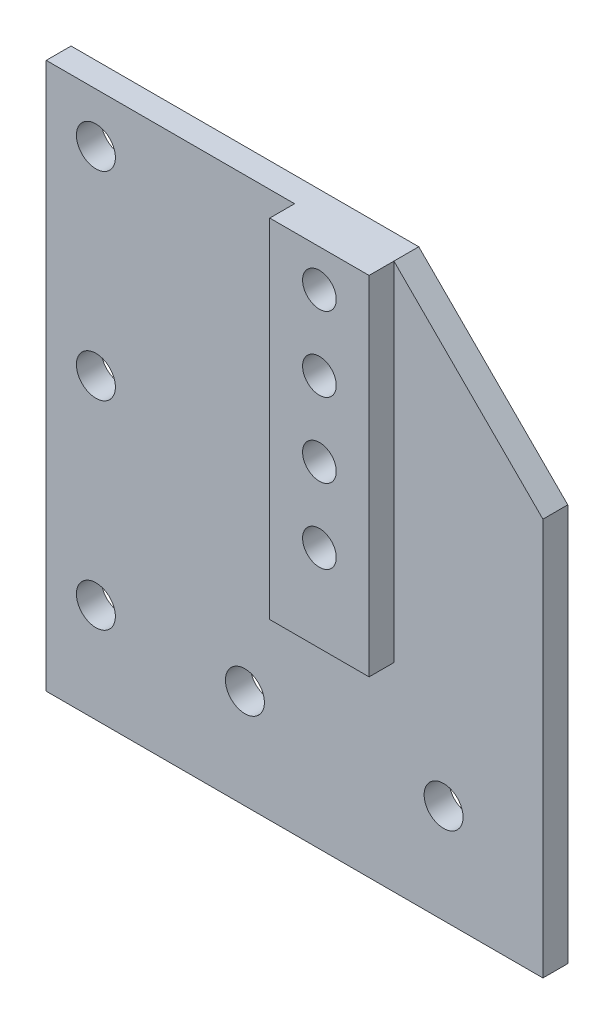
SolidWorks part; units mm, degrees
ref_plane "Front Plane" through (0, 0, 0) normal (0, 0, 1) x (1, 0, 0)
ref_plane "Top Plane" through (0, 0, 0) normal (0, 1, 0) x (1, 0, 0)
ref_plane "Right Plane" through (0, 0, 0) normal (1, 0, 0) x (0, 0, -1)
sketch "Sketch1" plane through (0, 0, 0) normal (0, 0, 1) x (1, 0, 0)
  line L0 (-254, -12.7) -> (-266.7, -12.7)
  line L2 (-266.7, 57.15) -> (-254, 57.15)
  line L3 (-254, -16.7024) -> (-254, 609.6) construction
  line L4 (-254, -12.7) -> (-203.2, -12.7)
  line L5 (-254, 57.15) -> (-222.25, 57.15)
  line L6 (-203.2, -12.7) -> (-203.2, 12.7)
  line L7 (-254, 12.7) -> (254, 12.7) construction
  line L13 (-222.25, 57.15) -> (-203.2, 38.1)
  line L15 (-266.7, -12.7) -> (-266.7, 57.15)
  line L16 (-266.7, 609.6) -> (-266.7, -16.7024) construction
  line L17 (-203.2, 12.7) -> (-203.2, 38.1)
  dimension "D1" = 69.85
  dimension "D2" = 25.4
  dimension "D3" = 31.75
extrude "Boss-Extrude1" add sketch "Sketch1" along normal blind 3.175
sketch "Sketch2" plane through (0, 0, 3.175) normal (0, 0, 1) x (1, 0, 0)
  line L0 (-203.2, -12.7) -> (-203.2, 12.7) construction
  line L1 (-215.9, 0) -> (-241.3, 0) construction
  line L2 (-203.2, 0) -> (-215.9, 0) construction
  line L3 (-254, -12.7) -> (-266.7, -12.7) construction
  line L4 (-260.35, -12.7) -> (-260.35, 0) construction
  line L5 (-260.35, 0) -> (-260.35, 25.4) construction
  line L6 (-260.35, 25.4) -> (-260.35, 50.7989) construction
  line L7 (-260.35, 25.4) -> (-260.35, 50.8) construction
  line L8 (-254, 12.7) -> (254, 12.7) construction
  dimension "D1" = 12.7
  dimension "D2" = 25.4
  dimension "D3" = 12.7
  dimension "D4" = 25.4
  dimension "D5" = 25.3989
hole_wizard "#10 Clearance Hole1" positions "Sketch3" profile "Sketch4" hole size "#10" standard "ANSI Inch" end condition through all
sketch "Sketch3" plane through (0, 0, 3.175) normal (0, 0, 1) x (1, 0, 0)
  point P15 (-260.35, 50.7989)
  point P18 (-260.35, 25.4)
  point P21 (-260.35, 0)
  point P24 (-241.3, 0)
  point P27 (-215.9, 0)
sketch "Sketch4" plane through (-260.35, 50.7989, 3.175) normal (1, 0, 0) x (0, -1, 0)
  line L0 (0, 0) -> (0, 3.175)
  line L1 (0, 3.175) -> (2.4892, 3.175)
  line L2 (2.4892, 3.175) -> (2.4892, 0)
  line L5 (2.4892, 0) -> (0, 0)
  line L11 (0, -6.35) -> (0, 107.95) construction
  dimension "Thru Hole Dia." = 4.9784
  dimension "Thru Hole Depth" = 3.175
sketch "Sketch5" plane through (0, 0, 3.175) normal (0, 0, 1) x (1, 0, 0)
  line L0 (-222.25, 57.15) -> (-222.25, 50.8) construction
  line L1 (-222.25, 57.15) -> (-234.95, 57.15)
  line L3 (-234.95, 57.15) -> (-234.95, 12.7)
  line L4 (-222.25, 50.8) -> (-222.25, 12.7)
  line L5 (-222.25, 12.7) -> (-234.95, 12.7)
  line L6 (-222.25, 50.8) -> (-222.25, 57.15)
  line L7 (-222.25, 57.15) -> (-266.7, 57.15) construction
  point P7 (-222.25, 50.8)
  dimension "D3" = 38.1
extrude "Boss-Extrude2" add sketch "Sketch5" along normal blind 3.175
sketch "Sketch6" plane through (0, 0, 6.35) normal (0, 0, 1) x (1, 0, 0)
  line L0 (-228.6, 57.15) -> (-228.6, 52.3875) construction
  line L1 (-228.6, 52.3875) -> (-228.6, 42.8625) construction
  line L2 (-228.6, 42.8625) -> (-228.6, 33.3375) construction
  line L3 (-222.25, 57.15) -> (-234.95, 57.15) construction
  line L4 (-228.6, 33.3375) -> (-228.6, 23.8125) construction
  dimension "D1" = 9.525
  dimension "D2" = 4.7625
  dimension "D3" = 9.525
  dimension "D4" = 9.525
hole_wizard "#8 Clearance Hole1" positions "Sketch7" profile "Sketch8" hole size "#8" standard "ANSI Inch" end condition through all
sketch "Sketch7" plane through (0, 0, 6.35) normal (0, 0, 1) x (1, 0, 0)
  point P0 (-228.6, 42.8625)
  point P3 (-228.6, 52.3875)
  point P7 (-228.6, 33.3375)
  point P10 (-228.6, 23.8125)
sketch "Sketch8" plane through (-228.6, 42.8625, 6.35) normal (1, 0, 0) x (0, -1, 0)
  line L0 (0, 0) -> (0, 6.35)
  line L1 (0, 6.35) -> (2.1526, 6.35)
  line L2 (2.1526, 6.35) -> (2.1526, 0)
  line L5 (2.1526, 0) -> (0, 0)
  line L11 (0, -6.35) -> (0, 107.95) construction
  dimension "Thru Hole Dia." = 4.3053
  dimension "Thru Hole Depth" = 6.35
